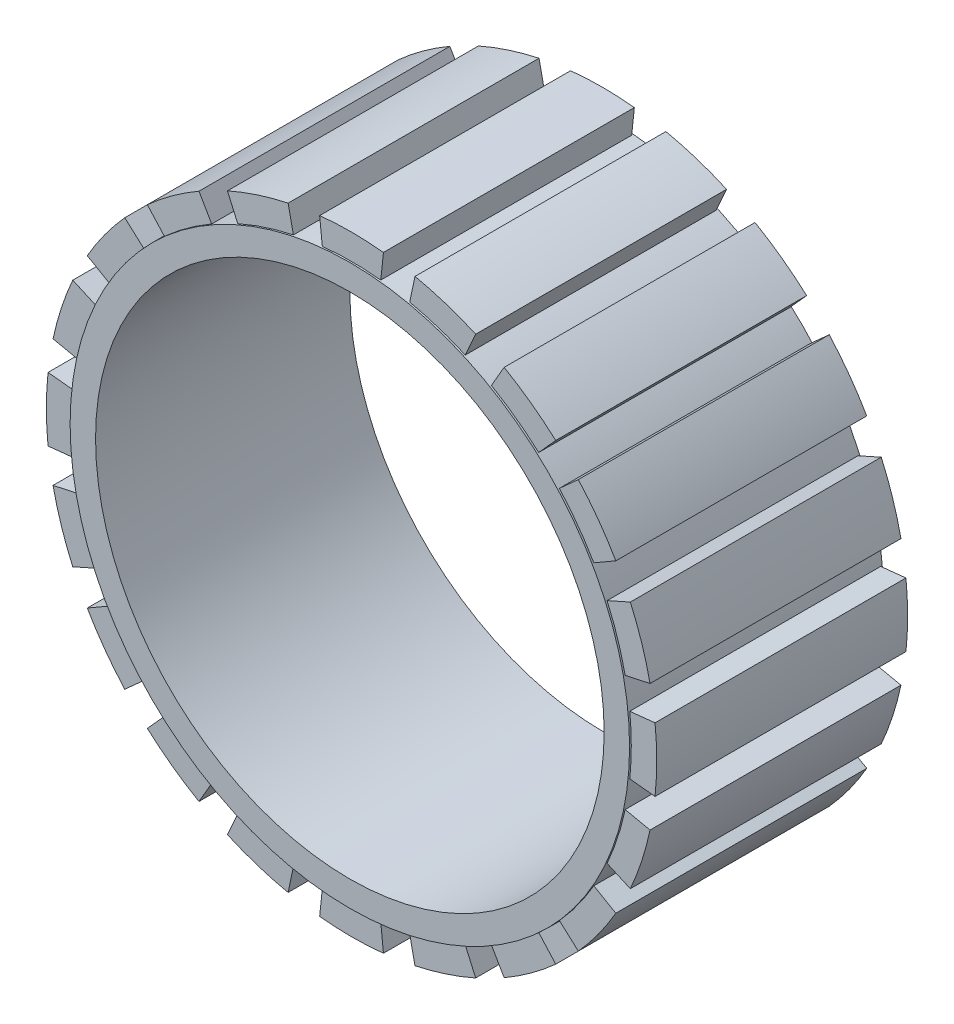
SolidWorks part; units mm, degrees
ref_plane "Front Plane" through (0, 0, 0) normal (0, 0, 1) x (1, 0, 0)
ref_plane "Top Plane" through (0, 0, 0) normal (0, 1, 0) x (1, 0, 0)
ref_plane "Right Plane" through (0, 0, 0) normal (1, 0, 0) x (0, 0, -1)
sketch "Sketch1" plane through (0, 0, 0) normal (0, 0, 1) x (1, 0, 0)
  circle A0 centre (0, 0) radius 15
  circle A1 centre (0, 0) radius 16.5
  dimension "D1" = 30
  dimension "D2" = 1.5
extrude "Boss-Extrude1" add sketch "Sketch1" along normal blind 15
ref_plane "Plane1" through (0, 0, 0.1) normal (0, 0, -1) x (-1, 0, 0)
sketch "Sketch2" plane through (0, 0, 0.1) normal (0, 0, -1) x (-1, 0, 0)
  line L0 (0, 0) -> (0, 15) construction
  line L1 (0, 0) -> (2.5812, 16.2969) construction
  line L2 (0, 0) -> (-2.5812, 16.2969) construction
  line L3 (-1.8815, 17.9014) -> (-1.7247, 16.4096)
  line L4 (1.8815, 17.9014) -> (1.7247, 16.4096)
  circle A0 centre (0, 0) radius 16.5 construction
  circle A1 centre (0, 0) radius 16.5 construction
  arc A2 (-1.7247, 16.4096) -> (1.7247, 16.4096) centre (0, 0) cw
  arc A3 (-1.8815, 17.9014) -> (1.8815, 17.9014) centre (0, 0) cw
  circle A4 centre (0, 0) radius 15 construction
  dimension "D3" = 1.5
  dimension "D1" = 18
  dimension "D2" = 6
extrude "Boss-Extrude3" add sketch "Sketch2" against normal offset from surface (14.8 mm away) 0.1 up to face at (16.5, 0, 15)
ref_axis "Axis1" through (0, 0, 15) along (0, 0, -1)
pattern_circular "CirPattern1" count 20 over 360 about axis through (0, 0, 15) along (0, 0, -1) of "Boss-Extrude3"
